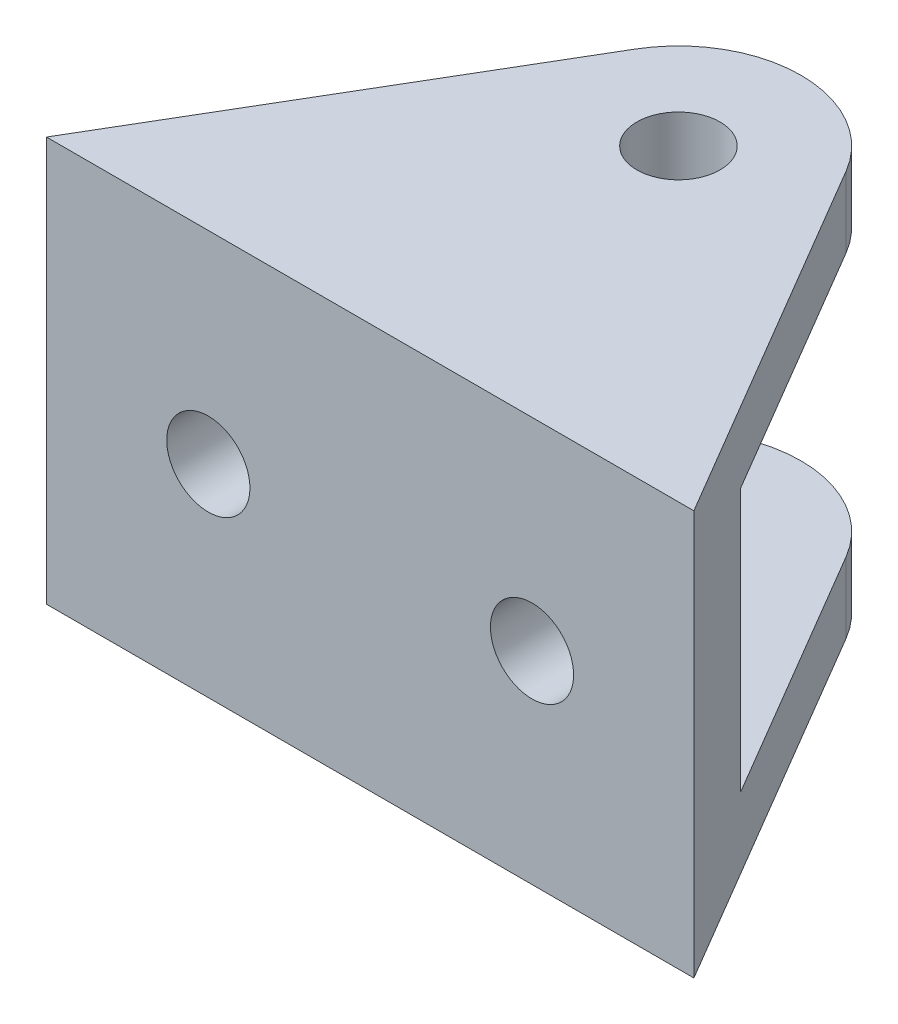
SolidWorks part; units mm, degrees
material "6061-T6 (SS)"
ref_plane "X-Y Datum" through (0, 0, 0) normal (0, 0, 1) x (1, 0, 0)
ref_plane "X-Z Datum" through (0, 0, 0) normal (0, 1, 0) x (1, 0, 0)
ref_plane "Y-Z Datum" through (0, 0, 0) normal (1, 0, 0) x (0, 0, -1)
sketch "Sketch1" plane through (0, 0, 0) normal (1, 0, 0) x (0, 0, -1)
  line L0 (0, 0) -> (0, 31.75)
  line L1 (0, 31.75) -> (43.2881, 31.75)
  line L2 (43.2881, 31.75) -> (43.2881, 26.2001)
  line L3 (43.2881, 26.2001) -> (8.89, 26.2001)
  line L4 (8.89, 26.2001) -> (8.89, 5.5499)
  line L5 (8.89, 5.5499) -> (43.2881, 5.5499)
  line L6 (43.2881, 5.5499) -> (43.2881, 0)
  line L7 (43.2881, 0) -> (0, 0)
  line L8 (30.5881, 31.75) -> (30.5881, 0) construction
  dimension "D1" = 20.6502
  dimension "D2" = 31.75
  dimension "D3" = 12.7
  dimension "D4" = 8.89
extrude "Boss-Extrude1" add sketch "Sketch1" along normal blind 50.8
sketch "Sketch2" plane through (0, 0, -8.89) normal (0, 0, -1) x (-1, 0, 0)
  line L0 (-50.8, 15.875) -> (0, 15.875) construction
  line L1 (-50.8, 5.5499) -> (-50.8, 26.2001) construction
  line L2 (0, 5.5499) -> (0, 26.2001) construction
  line L3 (-25.4, 5.5499) -> (-25.4, 26.2001) construction
  line L4 (-50.8, 5.5499) -> (0, 5.5499) construction
  line L5 (-50.8, 26.2001) -> (0, 26.2001) construction
  point P6 (-38.1, 15.875)
  point P7 (-12.7, 15.875)
  dimension "D1" = 25.4
  dimension "D2" = 12.7
hole_wizard "CBORE for 1/4 Binding Head Machine Screw1" positions "Sketch2" profile "Sketch3" counterbore size "1/4" standard "ANSI Inch" end condition through all
sketch "Sketch3" plane through (12.7, 15.875, -8.89) normal (1, 0, 0) x (0, 1, 0)
  line L0 (0, 0) -> (0, 8.89)
  line L1 (0, 8.89) -> (3.2639, 8.89)
  line L3 (3.2639, 8.89) -> (3.2639, 3.302)
  line L4 (3.2639, 3.302) -> (7.1437, 3.302)
  line L5 (7.1437, 3.302) -> (7.1437, 0)
  line L7 (7.1437, 0) -> (0, 0)
  line L11 (0, -6.35) -> (0, 107.95) construction
  dimension "Thru Hole Dia." = 6.5278
  dimension "Thru Hole Depth" = 8.89
  dimension "C'Bore Dia." = 14.2875
  dimension "C'Bore Depth" = 3.302
sketch "Sketch4" plane through (0, 0, 0) normal (0, -1, 0) x (1, 0, 0)
  line L0 (25.4, 0) -> (25.4, -43.2881) construction
  line L1 (50.8, 0) -> (0, 0) construction
  line L2 (50.8, -43.2881) -> (0, -43.2881) construction
  line L3 (17.1156, -29.0671) -> (0, 0)
  line L4 (33.6844, -29.0671) -> (50.8, 0)
  line L5 (0, 0) -> (0, -43.2881)
  line L6 (0, -43.2881) -> (50.8, -43.2881)
  line L7 (50.8, -43.2881) -> (50.8, 0)
  circle A0 centre (25.4, -24.189) radius 3.2639
  arc A1 (17.1156, -29.0671) -> (33.6844, -29.0671) centre (25.4, -24.189) ccw
  dimension "D1" = 6.5278
  dimension "D2" = 6.35
extrude "Cut-Extrude1" cut sketch "Sketch4" against normal up to surface (31.75 mm away) up to face at (25.4, 31.75, -21.644)
